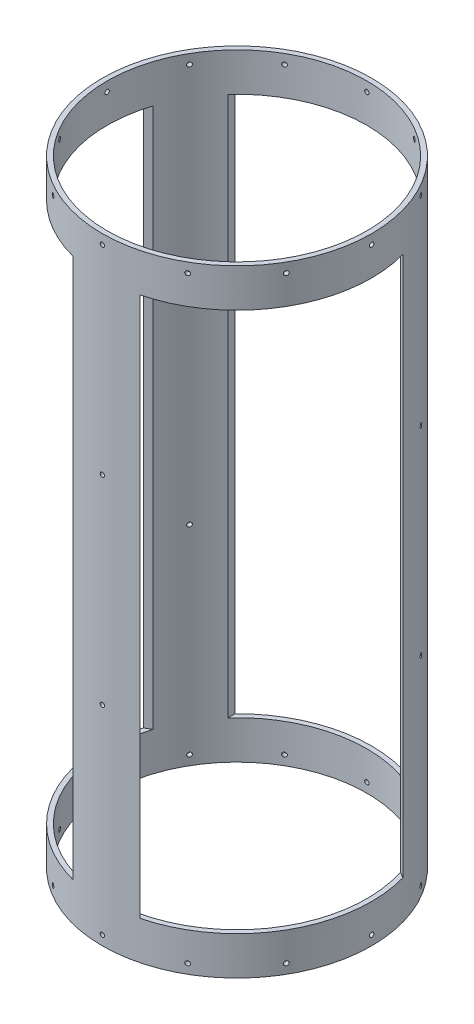
SolidWorks part; units mm, degrees
material "6061-T6 (SS)"
ref_plane "Front Plane" through (0, 0, 0) normal (0, 0, 1) x (1, 0, 0)
ref_plane "Top Plane" through (0, 0, 0) normal (0, 1, 0) x (1, 0, 0)
ref_plane "Right Plane" through (0, 0, 0) normal (1, 0, 0) x (0, 0, -1)
sketch "Sketch1" plane through (0, 0, 0) normal (0, 1, 0) x (1, 0, 0)
  circle A0 centre (0, 0) radius 88.9
  circle A1 centre (0, 0) radius 85.725
  dimension "D1" = 177.8
  dimension "D2" = 171.45
extrude "Boss-Extrude1" add sketch "Sketch1" along normal mid plane 407.162
sketch "Sketch2" plane through (0, 0, 0) normal (0, 0, 1) x (1, 0, 0)
  line L0 (85.725, 203.581) -> (-85.725, 203.581) construction
  line L1 (-63.5, -178.181) -> (63.5, -178.181)
  line L2 (-63.5, -178.181) -> (-63.5, 178.181)
  line L3 (-63.5, 178.181) -> (63.5, 178.181)
  line L4 (63.5, -178.181) -> (63.5, 178.181)
  line L5 (-63.5, -178.181) -> (63.5, 178.181) construction
  line L6 (-63.5, 178.181) -> (63.5, -178.181) construction
  line L7 (88.9, -203.581) -> (88.9, 203.581) construction
  point P0 (0, 0)
  dimension "D1" = 25.4
  dimension "D2" = 25.4
extrude "Cut-Extrude1" cut sketch "Sketch2" against normal up to surface (62.217 mm away) up to face at (0, 203.581, 88.9)
pattern_circular "CirPattern1" count 3 over 360 about axis through (0, 203.581, 0) along (0, -1, 0) of "Cut-Extrude1"
ref_plane "Plane1" through (88.9, 0, 0) normal (1, 0, 0) x (0, 0, -1)
sketch "Sketch4" plane through (88.9, 0, 0) normal (1, 0, 0) x (0, 0, -1)
  line L0 (0, 97.79) -> (0, -97.79) construction
  line L1 (88.9, 203.581) -> (-88.9, 203.581) construction
  circle A0 centre (0, 197.231) radius 1.4351
  dimension "D1" = 2.8702
  dimension "D2" = 6.35
extrude "Cut-Extrude3" cut sketch "Sketch4" against normal blind 15.24
pattern_circular "CirPattern3" count 12 over 360 about axis through (0, 203.581, 0) along (0, -1, 0) of "Cut-Extrude3"
mirror "Mirror1" about plane through (0, 0, 0) normal (0, 1, 0) of "Cut-Extrude3", "CirPattern3"
ref_plane "Plane2" through (0, 0, 88.9) normal (0, 0, 1) x (1, 0, 0)
sketch "Sketch5" plane through (0, 0, 88.9) normal (0, 0, 1) x (1, 0, 0)
  circle A0 centre (0, -65.7606) radius 1.4351
  circle A1 centre (0, 65.7606) radius 1.4351
  circle A2 centre (0, 197.231) radius 1.4351 construction
  circle A3 centre (0, -197.231) radius 1.4351 construction
  dimension "D1" = 131.4704
  dimension "D2" = 131.4704
  dimension "D3" = 2.8702
  dimension "D4" = 2.8702
extrude "Cut-Extrude4" cut sketch "Sketch5" against normal blind 46.482
pattern_circular "CirPattern4" count 3 over 360 about axis through (0, 203.581, 0) along (0, -1, 0) of "Cut-Extrude4"
